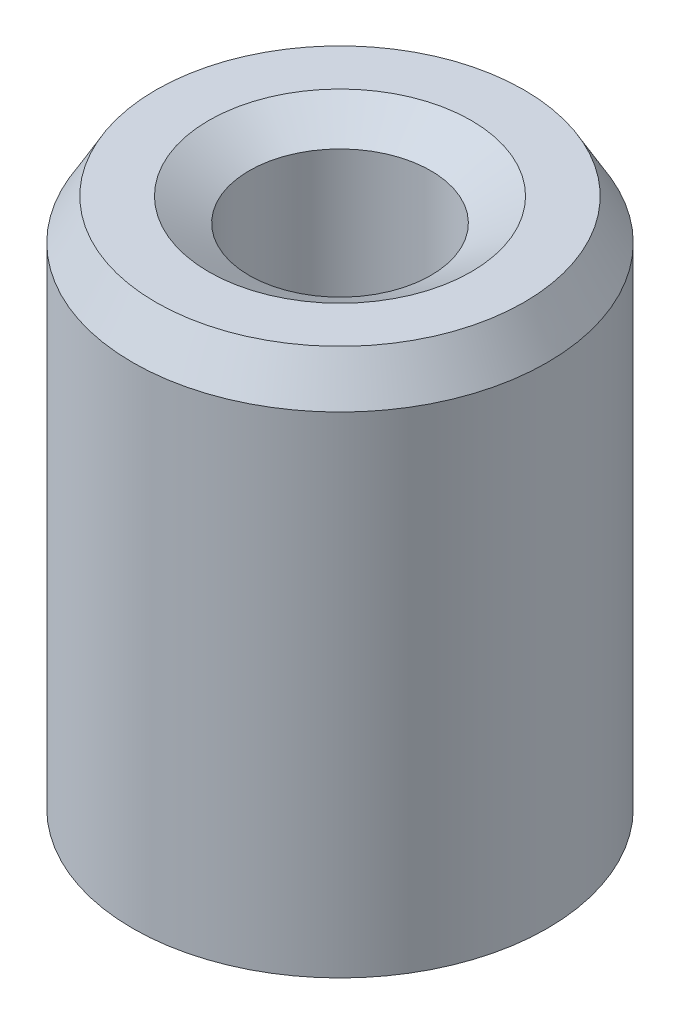
SolidWorks part; units mm, degrees
ref_plane "Front Plane" through (0, 0, 0) normal (0, 0, 1) x (1, 0, 0)
ref_plane "Top Plane" through (0, 0, 0) normal (0, 1, 0) x (1, 0, 0)
ref_plane "Right Plane" through (0, 0, 0) normal (1, 0, 0) x (0, 0, -1)
sketch "Sketch1" plane through (0, 0, 0) normal (0, 1, 0) x (1, 0, 0)
  circle A0 centre (0, 0) radius 10
  dimension "SLEEVE_OD" = 20
extrude "Boss-Extrude1" add sketch "Sketch1" along normal blind 26.7104
sketch "Sketch2" plane through (0, 0, 0) normal (0, 1, 0) x (1, 0, 0)
  circle A0 centre (0, 0) radius 4.3791
  dimension "BORE_D" = 8.7583
extrude "Cut-Extrude1" cut sketch "Sketch2" along normal through all
chamfer "Chamfer1" distance 1.9489 angle 30 4 edges at (0, 26.7104, 4.3791) (0, 0, 4.3791) (0, 0, 10) (0, 26.7104, 10) first distance on face at (0, 26.7104, 4.3791) first distance on face at (0, 0, 4.3791) first distance on face at (0, 26.7104, 10)
